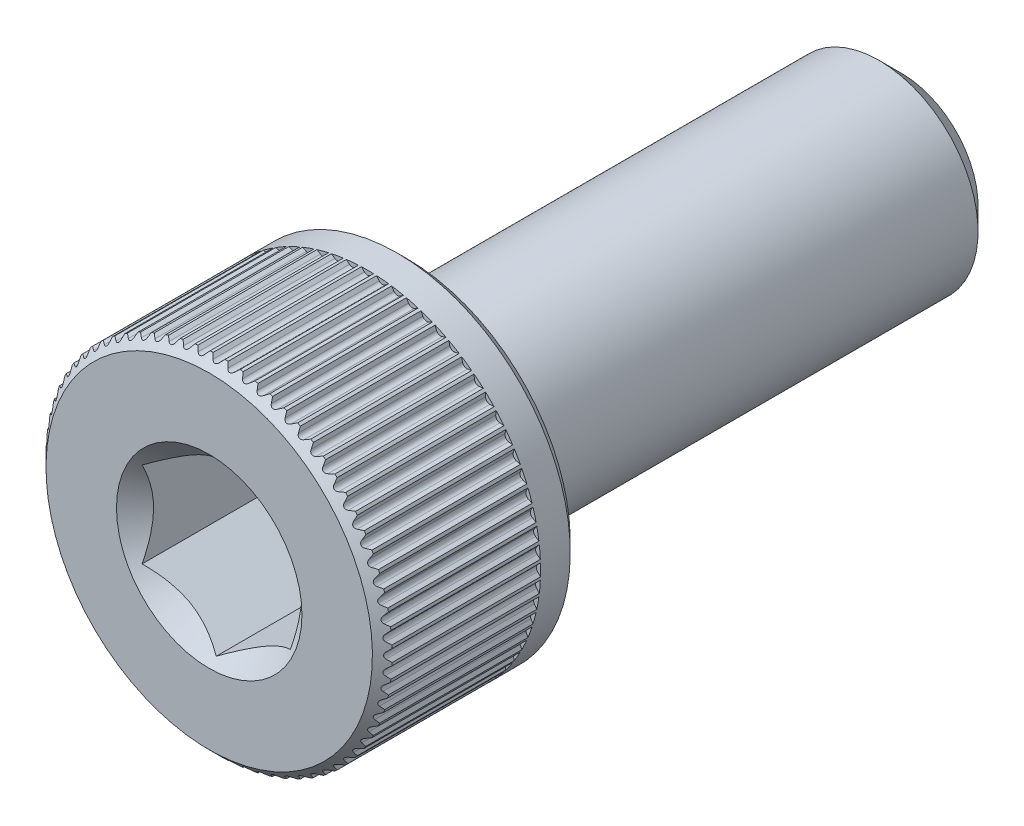
SolidWorks part; units mm, degrees
ref_plane "Front Plane" through (0, 0, 0) normal (0, 0, 1) x (1, 0, 0)
ref_plane "Top Plane" through (0, 0, 0) normal (0, 1, 0) x (1, 0, 0)
ref_plane "Right Plane" through (0, 0, 0) normal (1, 0, 0) x (0, 0, -1)
sketch "Sketch1" plane through (0, 0, 0) normal (1, 0, 0) x (0, 0, -1)
  line L0 (-7, 0) -> (7, 0) construction
  line L1 (7, 0) -> (7, 1.5453) construction
  line L2 (7, 1.5453) -> (6.5453, 2) construction
  line L3 (6.5453, 2) -> (6.475, 2) construction
  line L4 (6.475, 2) -> (-3, 2) construction
  line L5 (-3, 2) -> (-3, 3.5) construction
  line L6 (-3, 3.5) -> (-7, 3.5) construction
  line L7 (-7, 3.5) -> (-7, 0) construction
  line L8 (7, 1.5453) -> (7, 2) construction
  line L9 (6.9562, 2.0758) -> (7.3062, 1.4696) construction
  line L10 (7.3062, 1.4696) -> (7.6562, 2.0758) construction
  line L11 (7.6562, 2.0758) -> (6.9562, 2.0758) construction
  line L12 (7.3062, 2.0758) -> (7.3062, 2) construction
  line L13 (7.3062, 1.4696) -> (7.3062, 1.5453) construction
  line L14 (7.2625, 1.5453) -> (7.35, 1.5453) construction
  line L15 (7, 2) -> (7.6125, 2) construction
  line L16 (6.9781, 2.0379) -> (7.6344, 2.0379) construction
  line L17 (7, 0) -> (7, -2) construction
  line L18 (-3.2, 3.5) -> (-3, 3.3) construction
  line L19 (-6.8, 3.5) -> (-7, 3.3) construction
  line L20 (-3, 2) -> (-3, 0) construction
  line L21 (-3, 1) -> (0.3333, 1) construction
  line L22 (0.3333, 1) -> (3.6667, 1) construction
  line L23 (3.6667, 1) -> (7, 1) construction
  line L24 (0.3333, 1) -> (0.3333, 2) construction
  line L25 (0.3333, 2) -> (0.3333, 3.5) construction
  line L26 (3.6667, 1) -> (3.6667, 3.5) construction
  point P0 (-7, 1.5)
  point P3 (5.25, 2)
  point P4 (0, 0)
  point P18 (3.6667, 2)
  point P22 (7.3062, 1.5453)
  point P24 (6.475, 2)
  point P25 (7.3062, 2)
  point P28 (7.3062, 2.0379)
  point P29 (5.25, -2)
  point P30 (0.3333, 2)
  point P31 (-5, 3.5)
  point P37 (-3.7, 3.5)
  point P38 (-6.7, 3.5)
  point P45 (0.3333, 1)
  point P46 (3.6667, 1)
  dimension "D2" = 0.0875
  dimension "D7" = 0.2
  dimension "D8" = 0.2
  dimension "D9" = 0.2
  dimension "D10" = 0.1
  dimension "D11" = 0.5
  dimension "Drive Size" = 3
  dimension "Head Diameter" = 7
  dimension "Head Height" = 4
  dimension "Thread Pitch" = 0.7
  dimension "Thread Size" = 4
  dimension "Length" = 10
  dimension "D12" = 0.525
  dimension "D4" = 1.75
  dimension "D3" = 45
sketch "Sketch2" plane through (0, 0, 0) normal (1, 0, 0) x (0, 0, -1)
  line L0 (-7, 0) -> (-7, 3.3)
  line L1 (-6.8, 3.5) -> (-3.2, 3.5)
  line L2 (-3, 3.3) -> (-3, 2.2)
  line L4 (6.5453, 2) -> (7, 1.5453)
  line L5 (7, 1.5453) -> (7, 0)
  line L6 (-3, 3.5) -> (-7, 3.5) construction
  line L7 (7, 0) -> (-7, 0)
  line L8 (-6.8, 3.5) -> (-7, 3.3) construction
  line L10 (-6.8, 3.5) -> (-7, 3.3)
  line L14 (-3.2, 3.5) -> (-3, 3.3) construction
  line L16 (-3.2, 3.5) -> (-3, 3.3)
  line L17 (-3, 2) -> (-3, 3.5) construction
  line L19 (-2.8, 2) -> (6.5453, 2)
  line L20 (6.475, 2) -> (-3, 2) construction
  arc A1 (-3, 2.2) -> (-2.8, 2) centre (-2.8, 2.2) ccw
  dimension "D3" = 0.2
revolve "Revolve1" add sketch "Sketch2" angle 360 about L7
sketch "Sketch3" plane through (0, 0, 7) normal (0, 0, 1) x (1, 0, 0)
  line L1 (1.5, -0.866) -> (1.5, 0.866)
  line L2 (1.5, 0.866) -> (0, 1.7321)
  line L3 (0, 1.7321) -> (-1.5, 0.866)
  line L4 (-1.5, 0.866) -> (-1.5, -0.866)
  line L5 (-1.5, -0.866) -> (0, -1.7321)
  line L6 (0, -1.7321) -> (1.5, -0.866)
  circle A0 centre (0, 0) radius 1.5 construction
  circle A1 centre (0, 0) radius 3.5 construction
  circle A2 centre (0, 0) radius 3.5 construction
  circle A3 centre (0, 0) radius 1.7321 construction
  point P13 (0, 0)
extrude "Cut-Extrude1" cut sketch "Sketch3" against normal offset from surface (3 mm away) 1 up to face at (0, 3.3, 3)
sketch "Sketch4" plane through (0, 0, 7) normal (0, 0, 1) x (1, 0, 0)
  circle A0 centre (0, 0) radius 1.875
  dimension "D1" = 3.75
extrude "Cut-Extrude2" cut sketch "Sketch4" against normal up to vertex (2 mm away) draft 45 up to point (0, 3.5, 5)
sketch "Sketch11" plane through (0, 0, 0) normal (1, 0, 0) x (0, 0, -1)
  line L0 (-7, 0) -> (7, 0) construction
  line L1 (-7, 0) -> (7, 0) construction
  line L2 (-1.125, 0) -> (-1.125, 2) construction
  line L3 (6.475, 2) -> (-3, 2) construction
  line L4 (5.125, 0) -> (5.125, 2) construction
  line L6 (7, 1.5453) -> (7, 2) construction
  point P2 (-1.125, 0)
  point P3 (5.125, 0)
  dimension "D1" = 1.875
  dimension "D2" = 1.875
sketch "Sketch6" [suppressed] plane through (0, 0, -7) normal (0, 0, -1) x (-1, 0, 0)
  circle A0 centre (0, 0) radius 2
curve "Helix/Spiral1" [suppressed] pitch 0.7 height 10.7 turns 15.2857
sketch "Sketch10" [suppressed] plane through (0, 0, 0) normal (1, 0, 0) x (0, 0, -1)
  line L0 (-2.8, -3.5) -> (-2.8, 3.5)
  line L5 (-7, 0) -> (7, 0) construction
  line L6 (-2.8, 2) -> (-2.8, -2) construction
  point P3 (-2.8, 0)
split "Split1" [suppressed] bodies to split 106
sketch "Sketch7" [suppressed] plane through (0, 0, 0) normal (1, 0, 0) x (0, 0, -1)
  line L0 (6.9781, 2.0379) -> (7.6344, 2.0379)
  line L1 (7.6344, 2.0379) -> (7.35, 1.5453)
  line L2 (7.35, 1.5453) -> (7.2625, 1.5453)
  line L3 (7.2625, 1.5453) -> (6.9781, 2.0379)
sweep "Cut-Sweep1" [suppressed] cut profiles "Sketch7" path "Helix/Spiral1"
sketch "Sketch8" [suppressed] plane through (0, 0, 0) normal (1, 0, 0) x (0, 0, -1)
  line L0 (-3, 0) -> (-3, 2)
  line L1 (-2.8, -2) -> (-2.8, 2) construction
  line L2 (-3, 2) -> (-2.8, 2)
  line L4 (-2.8, 2) -> (-1.6453, 0)
  line L5 (-1.6453, 0) -> (-3, 0)
  line L6 (6.475, 2) -> (-3, 2) construction
  line L7 (-7, 0) -> (7, 0) construction
  dimension "D1" = 60
revolve "Revolve2" [suppressed] add sketch "Sketch8" angle 360 about L5
ref_plane "Plane1" through (0, 0, 7) normal (0, 0, 1) x (1, 0, 0)
sketch "Sketch12" plane through (0, 0, 7) normal (0, 0, 1) x (1, 0, 0)
  line L0 (0, 0) -> (0.1221, 3.4979) construction
  line L1 (0, 0) -> (-0.1221, 3.4979) construction
  line L2 (0, 3.4125) -> (0, 3.5875) construction
  line L3 (-0.2118, 3.5875) -> (0.2118, 3.5875)
  line L4 (-0.2118, 3.5875) -> (-0.0628, 3.4385)
  line L5 (0.0628, 3.4385) -> (0.2118, 3.5875)
  circle A0 centre (0, 0) radius 3.5 construction
  arc A1 (-0.0628, 3.4385) -> (0.0628, 3.4385) centre (0, 3.5013) ccw
  point P9 (0, 3.5875)
  point P13 (0, 3.5)
  dimension "D2" = 0.0875
extrude "Cut-Extrude3" cut sketch "Sketch12" against normal blind 3.2
pattern_circular "CirPattern1" count 72 over 360 about axis through (0, 0, 7) along (0, 0, -1) of "Cut-Extrude3"
equation "\"D2@Sketch1\" = \"Thread Pitch@Sketch1\" / 8"
equation "\"D4@Helix/Spiral1\" = \"Thread Pitch@Sketch1\""
equation "\"D7@Sketch1\" = \"Head Height@Sketch1\" * .05"
equation "\"D8@Sketch1\"=\"D7@Sketch1\""
equation "\"D9@Sketch1\"=\"D7@Sketch1\""
equation "\"D10@Sketch1\"=\"D7@Sketch1\"/2"
equation "\"D11@Sketch1\"=\"D10@Sketch1\"*5"
equation "\"D4@Sketch1\"=\"Thread Pitch@Sketch1\"*2.5"
equation "\"D12@Sketch1\"=\"Thread Pitch@Sketch1\"*.75"
equation "\"D3@Helix/Spiral1\"=\"Length@Sketch1\"+\"Thread Pitch@Sketch1\""
equation "\"D3@Sketch2\" = \"Thread Size@Sketch1\" * 0.05"
equation "\"D1@Sketch11\"=\"Length@Sketch1\"*0.1875"
equation "\"D2@Sketch11\"=\"D1@Sketch11\""
equation "\"D2@Sketch12\"=\"Head Diameter@Sketch1\"*.0125"
equation "\"D1@Cut-Extrude3\"=\"Head Height@Sketch1\"*.8"
equation "\"D1@CirPattern1\"=\"D3@CirPattern1\"/(1.25*\"D1@Sketch12\")"
equation "\"D1@Sketch4\"=\"Drive Size@Sketch1\"*1.25"
